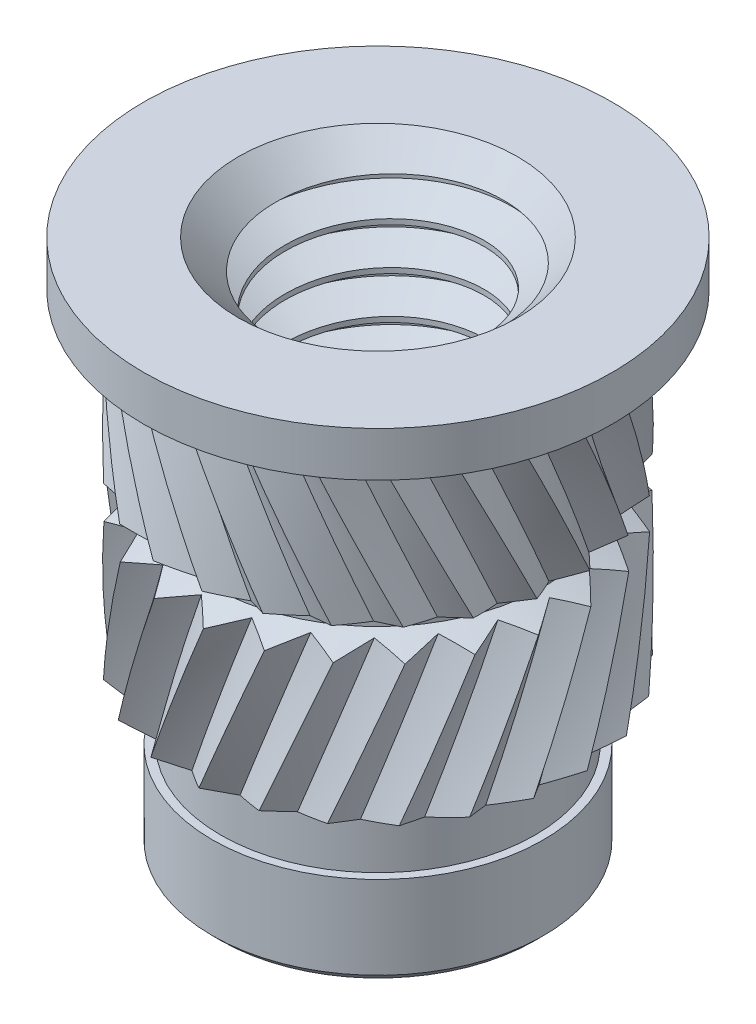
SolidWorks part; units mm, degrees
ref_plane "Front Plane" through (0, 0, 0) normal (0, 0, 1) x (1, 0, 0)
ref_plane "Top Plane" through (0, 0, 0) normal (0, 1, 0) x (1, 0, 0)
ref_plane "Right Plane" through (0, 0, 0) normal (1, 0, 0) x (0, 0, -1)
sketch "Sketch1" plane through (0, 0, 0) normal (0, 0, 1) x (1, 0, 0)
  line L0 (0, -2.8702) -> (0, 2.8702) construction
  line L1 (0, 2.8702) -> (0, 3.4002) construction
  line L2 (-2.7686, 3.4002) -> (2.7686, 3.4002) construction
  line L3 (-1.5, 2.8702) -> (1.5, 2.8702) construction
  line L4 (1.5, 2.8702) -> (1.5, 2.3702) construction
  line L5 (1.9558, -2.8702) -> (-1.9558, -2.8702) construction
  point P4 (0, 0)
  point P9 (0, 3.4002)
  point P12 (0, 2.8702)
  point P16 (0, -2.8702)
  dimension "Installed Length" = 5.7404
  dimension "Flange Thickness" = 0.53
  dimension "Flange Diameter" = 5.5372
  dimension "Thread Size" = 3
  dimension "Thread Pitch" = 0.5
  dimension "Small Dia" = 3.9116
sketch "Sketch2" plane through (0, 0, 0) normal (0, 1, 0) x (1, 0, 0)
  line L0 (1.9558, 0) -> (2.3622, 0) construction
  line L1 (1.9558, 0) -> (-1.9558, 0) construction
  line L2 (2.0574, 0) -> (2.4165, 0.4807)
  line L3 (-2.7686, 0) -> (2.7686, 0) construction
  line L4 (2.3622, 0) -> (2.7686, 0) construction
  line L5 (2.0574, 0) -> (2.4165, -0.4807)
  line L6 (0, 0) -> (2.4165, 0.4807) construction
  line L7 (0, 0) -> (2.4165, -0.4807) construction
  line L8 (0, 0) -> (2.342, -0.3083) construction
  line L9 (0, 0) -> (2.342, 0.3083) construction
  line L10 (0, 0) -> (1.6703, 1.6703) construction
  circle A0 centre (0, 0) radius 2.3622 construction
  arc A1 (2.4165, 0.4807) -> (2.4165, -0.4807) centre (0, 0) cw
  point P14 (2.0574, 0)
  point P15 (2.159, 0)
  point P16 (2.2606, 0)
  point P21 (2.4638, 0)
  point P22 (2.5654, 0)
  point P23 (2.667, 0)
  dimension "Knurl Length" = 22.5
  dimension "Pattern Angle" = 15
  dimension "Helix Angle" = 45
sketch "Sketch3" plane through (0, 0, 0) normal (0, 0, 1) x (1, 0, 0)
  line L0 (-2.7686, 3.4002) -> (-2.7686, 2.8702)
  line L1 (-2.7686, 2.8702) -> (-1.9558, 2.8702)
  line L2 (-1.9558, 2.8702) -> (-1.9558, 2.6549)
  line L3 (-1.9558, 2.6549) -> (-2.3622, 2.6549)
  line L4 (-2.3622, 2.6549) -> (-2.3622, 1.0548)
  line L5 (-2.3622, 1.0548) -> (-1.9558, 1.0548) construction
  line L6 (-1.9558, 1.0548) -> (-1.9558, 0.8395) construction
  line L7 (-1.9558, 0.8395) -> (-1.9558, 0.6243) construction
  line L8 (-1.9558, 0.6243) -> (-2.3622, 0.6243) construction
  line L9 (-2.3622, 0.6243) -> (-2.3622, -0.9759)
  line L10 (-2.3622, -0.9759) -> (-1.858, -1.1911)
  line L11 (-1.858, -1.1911) -> (-1.858, -1.791)
  line L12 (-1.858, -1.791) -> (-1.9558, -1.791)
  line L13 (-1.9558, -1.791) -> (-1.9558, -2.7724)
  line L14 (-1.9558, -2.7724) -> (-1.858, -2.8702)
  line L15 (-1.858, -2.8702) -> (-1.65, -2.8702)
  line L16 (1.9558, -2.8702) -> (-1.9558, -2.8702) construction
  line L17 (-1.65, -2.8702) -> (-1.5, -2.7202)
  line L18 (-1.5, -2.7202) -> (-1.5, 3.2502)
  line L19 (-1.5, 3.2502) -> (-1.65, 3.4002)
  line L20 (-2.7686, 3.4002) -> (2.7686, 3.4002) construction
  line L21 (-1.65, 3.4002) -> (-2.7686, 3.4002)
  line L22 (-1.5, 2.8702) -> (1.5, 2.8702) construction
  line L23 (-1.65, -2.8702) -> (-1.5, -2.8702) construction
  line L24 (-1.5, -2.8702) -> (-1.5, -2.7202) construction
  line L25 (-1.65, 3.4002) -> (-1.5, 3.4002) construction
  line L26 (-1.5, 3.4002) -> (-1.5, 3.2502) construction
  line L27 (0, 3.4002) -> (0, -2.8702) construction
  line L28 (-1.858, -1.1911) -> (-1.858, -0.9759) construction
  line L29 (-1.858, -0.9759) -> (-2.3622, -0.9759) construction
  line L30 (-2.3622, 0.6243) -> (-1.9558, 0.7978)
  line L31 (-1.9558, 0.7978) -> (-1.9558, 0.8813)
  line L32 (-1.9558, 0.8813) -> (-2.3622, 1.0548)
  point P36 (-2.3622, 2.8702)
  dimension "D1" = 3.3
  dimension "D2" = 3.716
  dimension "D3" = 3.8461
  dimension "D4" = 1.0792
  dimension "D5" = 0.2153
  dimension "D6" = 45
revolve "Revolve1" add sketch "Sketch3" angle 360 about L27
sketch "Sketch15" plane through (0, 0, 0) normal (0, 1, 0) x (1, 0, 0)
  line L0 (0, 0) -> (0, -1.5) construction
  circle A0 centre (0, 0) radius 1.5 construction
  point P7 (0, -1.5)
sketch "Sketch4" plane through (0, 0, 0) normal (0, 0, 1) x (1, 0, 0)
  line L1 (-1.5, 3.4002) -> (0, 3.4002)
  line L2 (-1.5, 3.4002) -> (-1.5, -2.8702)
  line L3 (-1.5, -2.8702) -> (0, -2.8702)
  line L4 (0, 3.4002) -> (0, -2.8702)
revolve "Revolve2" add sketch "Sketch4" angle 360 about L4
sketch "Sketch5" plane through (0, -2.8702, 0) normal (0, -1, 0) x (1, 0, 0)
  circle A1 centre (0, 0) radius 1.5
  circle A2 centre (0, 0) radius 1.5
  dimension "D1" = 0
curve "Helix/Spiral1" pitch 0.5 height 6.7704 turns 13.5408
sketch "Sketch6" plane through (0, 0, 0) normal (0, 0, 1) x (1, 0, 0)
  line L0 (1.5541, -2.839) -> (1.5541, -3.339) construction
  line L1 (1.5541, -3.339) -> (1.1211, -3.089) construction
  line L2 (1.1211, -3.089) -> (1.5541, -2.839) construction
  line L3 (1.1752, -3.0577) -> (1.1752, -3.1202)
  line L4 (1.5, -2.8702) -> (1.5, -3.3077) construction
  line L5 (1.5, -3.089) -> (1.5541, -3.089) construction
  line L6 (1.1211, -3.089) -> (1.1752, -3.089) construction
  line L7 (1.5271, -3.089) -> (1.5271, -3.3233) construction
  line L8 (1.1752, -3.0577) -> (1.5541, -2.839)
  line L9 (1.5541, -2.839) -> (1.5271, -3.3233)
  line L10 (1.5271, -3.3233) -> (1.1752, -3.1202)
  dimension "D1" = 0.5
  dimension "D2" = 0.0625
sweep "Cut-Sweep1" cut profiles "Sketch6" path "Helix/Spiral1" align with end faces yes
sketch "Sketch7" plane through (0, 0, 0) normal (0, 0, 1) x (1, 0, 0)
  line L0 (-1.65, -2.8702) -> (0, -1.2202)
  line L1 (0, -1.2202) -> (0, -2.8702)
  line L2 (1.9558, -2.8702) -> (-1.9558, -2.8702) construction
  line L3 (0, -2.8702) -> (-1.65, -2.8702)
  line L4 (-1.65, -2.8702) -> (-1.5, -2.7202) construction
  line L5 (0, -2.8702) -> (0, 2.8702) construction
revolve "Revolve3" add sketch "Sketch7" angle 360 about L1
sketch "Sketch8" plane through (0, 0, 0) normal (0, 0, 1) x (1, 0, 0)
  line L0 (-1.65, 3.4002) -> (0, 3.4002)
  line L1 (0, 3.4002) -> (0, 1.7502)
  line L2 (0, 1.7502) -> (-1.65, 3.4002)
  line L3 (-1.5, 3.2502) -> (-1.65, 3.4002) construction
revolve "Revolve4" add sketch "Sketch8" angle 360 about L1
sketch "Sketch9" plane through (0, 0, 0) normal (0, 0, 1) x (1, 0, 0)
  line L1 (-1.65, 3.4002) -> (0, 3.4002)
  line L2 (-1.65, 3.4002) -> (-1.65, -2.8702)
  line L3 (-1.65, -2.8702) -> (0, -2.8702)
  line L4 (0, 3.4002) -> (0, -2.8702)
revolve "Revolve5" add sketch "Sketch9" angle 360 about L4
combine bodies "Combine1" operation type subtract main body 109 bodies to subtract 108
ref_plane "Plane1" through (0, 0.8395, 0) normal (0, 1, 0) x (1, 0, 0)
sketch "Sketch10" plane through (0, 0.8395, 0) normal (0, 1, 0) x (1, 0, 0)
  circle A1 centre (0, 0) radius 2.3622
  circle A2 centre (0, 0) radius 2.3622 construction
curve "Helix/Spiral2" pitch 30.7685 height 1.923 radius 2.3622 left hand yes centre (0, 0.8395, 0) axis (0, 1, 0) start towards (1, 0, 0)
sketch "Sketch11" plane through (0, 0.8395, 0) normal (0, 1, 0) x (1, 0, 0)
  circle A1 centre (0, 0) radius 2.3622
  circle A2 centre (0, 0) radius 2.3622 construction
curve "Helix/Spiral3" pitch 36.7386 height 2.2962 radius 2.3622 centre (0, 0.8395, 0) axis (0, -1, 0) start towards (1, 0, 0)
sketch "Sketch12" plane through (0, 0.8395, 0) normal (0, 1, 0) x (1, 0, 0)
  line L4 (2.0574, 0) -> (2.4165, 0.4807) construction
  line L5 (2.0574, 0) -> (2.4165, -0.4807) construction
  line L6 (2.0574, 0) -> (2.4165, 0.4807)
  line L7 (2.0574, 0) -> (2.4165, -0.4807)
  arc A2 (2.4165, -0.4807) -> (2.4165, 0.4807) centre (0, 0) ccw construction
  arc A3 (2.4165, -0.4807) -> (2.4165, 0.4807) centre (0, 0) ccw
sweep "Cut-Sweep2" cut profiles "Sketch12" path "Helix/Spiral2" align with end faces yes
sketch "Sketch13" plane through (0, 0.8395, 0) normal (0, 1, 0) x (1, 0, 0)
  line L4 (2.0574, 0) -> (2.4165, 0.4807) construction
  line L5 (2.0574, 0) -> (2.4165, -0.4807) construction
  line L6 (2.0574, 0) -> (2.4165, 0.4807)
  line L7 (2.0574, 0) -> (2.4165, -0.4807)
  arc A2 (2.4165, -0.4807) -> (2.4165, 0.4807) centre (0, 0) ccw construction
  arc A3 (2.4165, -0.4807) -> (2.4165, 0.4807) centre (0, 0) ccw
sweep "Cut-Sweep3" cut profiles "Sketch13" path "Helix/Spiral3" align with end faces yes
pattern_circular "CirPattern1" count 24 over 360 about axis through (0, -2.8702, 0) along (0, 1, 0) of "Cut-Sweep3", "Cut-Sweep2" reverse direction yes
equation "\"D1@Sketch3\" = \"Thread Size@Sketch1\" * 1.1"
equation "\"D2@Sketch3\" = \"Small Dia@Sketch1\" * .95"
equation "\"D3@Sketch3\" = \"Installed Length@Sketch1\" * .67"
equation "\"D4@Sketch3\" = \"Installed Length@Sketch1\" * .188"
equation "\"D5@Sketch3\" = \"Installed Length@Sketch1\" * .0375"
equation "\"D3@Helix/Spiral1\"=\"Installed Length@Sketch1\"+\"Flange Thickness@Sketch1\"+\"Thread Pitch@Sketch1\""
equation "\"D3@Helix/Spiral2\"=\"Installed Length@Sketch1\"*.335"
equation "\"D4@Helix/Spiral2\"=(\"Installed Length@Sketch1\"*.335)*(360/\"Helix Angle@Sketch2\")"
equation "\"D3@Helix/Spiral3\"=\"Installed Length@Sketch1\"*.4"
equation "\"D1@CirPattern1\"=(360/\"Pattern Angle@Sketch2\")*1"
equation "\"D4@Helix/Spiral1\"=\"Thread Pitch@Sketch1\""
equation "\"D1@Sketch6\"=\"Thread Pitch@Sketch1\""
equation "\"D2@Sketch6\"=\"Thread Pitch@Sketch1\"/8"
